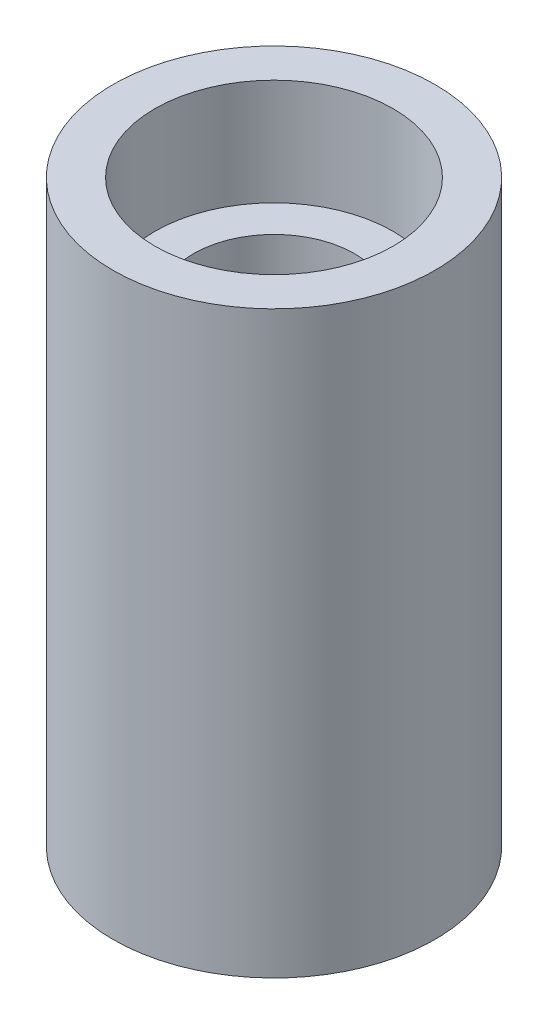
SolidWorks part; units mm, degrees
ref_plane "Front Plane" through (0, 0, 0) normal (0, 0, 1) x (1, 0, 0)
ref_plane "Top Plane" through (0, 0, 0) normal (0, 1, 0) x (1, 0, 0)
ref_plane "Right Plane" through (0, 0, 0) normal (1, 0, 0) x (0, 0, -1)
sketch "Sketch1" plane through (0, 0, 0) normal (0, 1, 0) x (1, 0, 0)
  circle A0 centre (0, 0) radius 5
  circle A1 centre (0, 0) radius 2.5
  dimension "D1" = 10
  dimension "D2" = 5
extrude "Boss-Extrude1" add sketch "Sketch1" along normal blind 18
sketch "Sketch2" plane through (0, 0, 0) normal (0, -1, 0) x (1, 0, 0)
  circle A0 centre (0, 0) radius 2.5 construction
  circle A1 centre (0, 0) radius 2.5
  circle A2 centre (0, 0) radius 3.7
  dimension "D1" = 7.4
extrude "Cut-Extrude1" cut sketch "Sketch2" against normal blind 3.3
extrude "Cut-Extrude2" cut sketch "Sketch2<2>" along normal blind 3.3 from surface starting at face at (0, 18, 5)
sketch "Sketch2<2>" plane through (0, 0, 0) normal (0, -1, 0) x (1, 0, 0) same geometry as "Sketch2"
